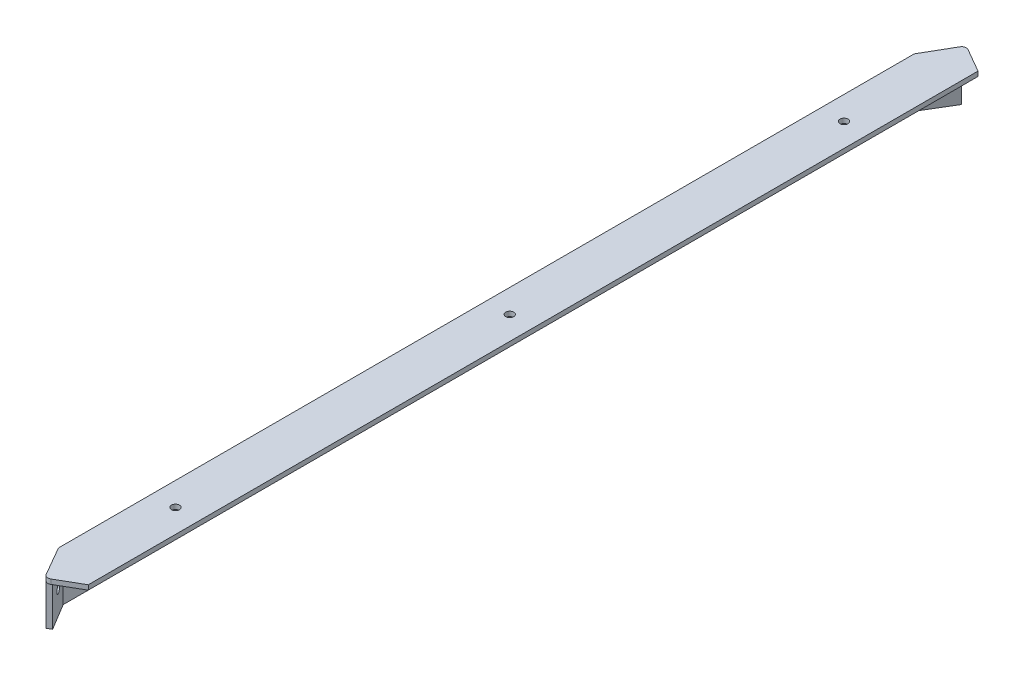
SolidWorks part; units mm, degrees
material "1.0116 (S235J2G3)"
ref_plane "Front Plane" through (0, 0, 0) normal (0, 0, 1) x (1, 0, 0)
ref_plane "Top Plane" through (0, 0, 0) normal (0, 1, 0) x (1, 0, 0)
ref_plane "Right Plane" through (0, 0, 0) normal (1, 0, 0) x (0, 0, -1)
sketch "Sketch1" plane through (0, 0, 0) normal (0, 0, 1) x (1, 0, 0)
  line L6 (0, 0) -> (0, 70)
  line L7 (0, 70) -> (70, 70)
  line L8 (70, 70) -> (70, 63)
  line L9 (70, 63) -> (7, 63)
  line L10 (7, 63) -> (7, 0)
  line L11 (7, 0) -> (0, 0)
  dimension "D1" = 70
  dimension "D2" = 70
  dimension "D3" = 7
  dimension "D4" = 7
extrude "Boss-Extrude1" add sketch "Sketch1" along normal blind 640
sketch "Sketch2" plane through (0, 0, 0) normal (0, 1, 0) x (1, 0, 0)
  line L0 (0, -640) -> (25, -683.3013)
  line L1 (25, -683.3013) -> (31.0622, -679.8013)
  line L2 (31.0622, -679.8013) -> (7, -640)
  line L3 (0, -640) -> (7, -640) construction
  line L4 (7, -640) -> (0, -640)
  line L5 (0, -640) -> (0, 0) construction
  dimension "D1" = 46.5095
  dimension "D2" = 50
  dimension "D3" = 210
  dimension "D4" = 7
extrude "Boss-Extrude2" add sketch "Sketch2" along normal blind 63
sketch "Sketch9" plane through (0, 63, 0) normal (0, 1, 0) x (1, 0, 0)
  line L0 (0, -640) -> (25, -683.3013)
  line L1 (34.5622, -685.8634) -> (70, -665.4034)
  line L2 (70, -665.4034) -> (70, -640)
  line L3 (70, -640) -> (0, -640)
  arc A0 (25, -683.3013) -> (34.5622, -685.8634) centre (31.0622, -679.8013) ccw
  dimension "D5" = 14
  dimension "D2" = 40.9201
  dimension "D1" = 90
  dimension "D3" = 90
  dimension "D4" = 60
  dimension "D6" = 7
  dimension "D7" = 7
extrude "Boss-Extrude4" add sketch "Sketch9" along normal blind 7
sketch "Sketch10" plane through (-278.2276, 0, 168.2047) normal (0.8558, 0, -0.5174) x (-0.5174, 0, -0.8558)
  line L0 (-597.822, 63) -> (-597.822, 0) construction
  line L1 (-597.822, 0) -> (-551.3126, 0) construction
  circle A0 centre (-572.822, 35) radius 6
  dimension "D1" = 12
  dimension "D2" = 25
  dimension "D3" = 35
extrude "Cut-Extrude3" cut sketch "Sketch10" against normal blind 7
sketch "Sketch21" plane through (0, 0, 0) normal (0, 0, -1) x (-1, 0, 0)
  line L0 (0, 70) -> (-70, 70) construction
  line L1 (-70, 70) -> (-70, 0) construction
  line L2 (-70, 0) -> (0, 0) construction
  line L3 (0, 0) -> (0, 69.2595) construction
fillet "Fillet5" radius 5 2 edges at (19.0311, 63, 659.9006) (7, 63, 320)
mirror "Mirror6" about plane through (0, 0, 0) normal (0, 0, 1) of bodies 107 108
sketch "Sketch22" plane through (0, 70, 0) normal (0, 1, 0) x (1, 0, 0)
  line L0 (70, 0) -> (0, 0) construction
  line L1 (0, -38.5) -> (0, 38.5) construction
  circle A0 centre (35, 0) radius 6
  circle A1 centre (35, 500) radius 6
  circle A2 centre (35, -500) radius 6
  dimension "D1" = 12
  dimension "D2" = 12
  dimension "D3" = 12
  dimension "D4" = 500
  dimension "D5" = 500
  dimension "D6" = 35
  dimension "D7" = 35
extrude "Cut-Extrude4" cut sketch "Sketch22" against normal blind 10
